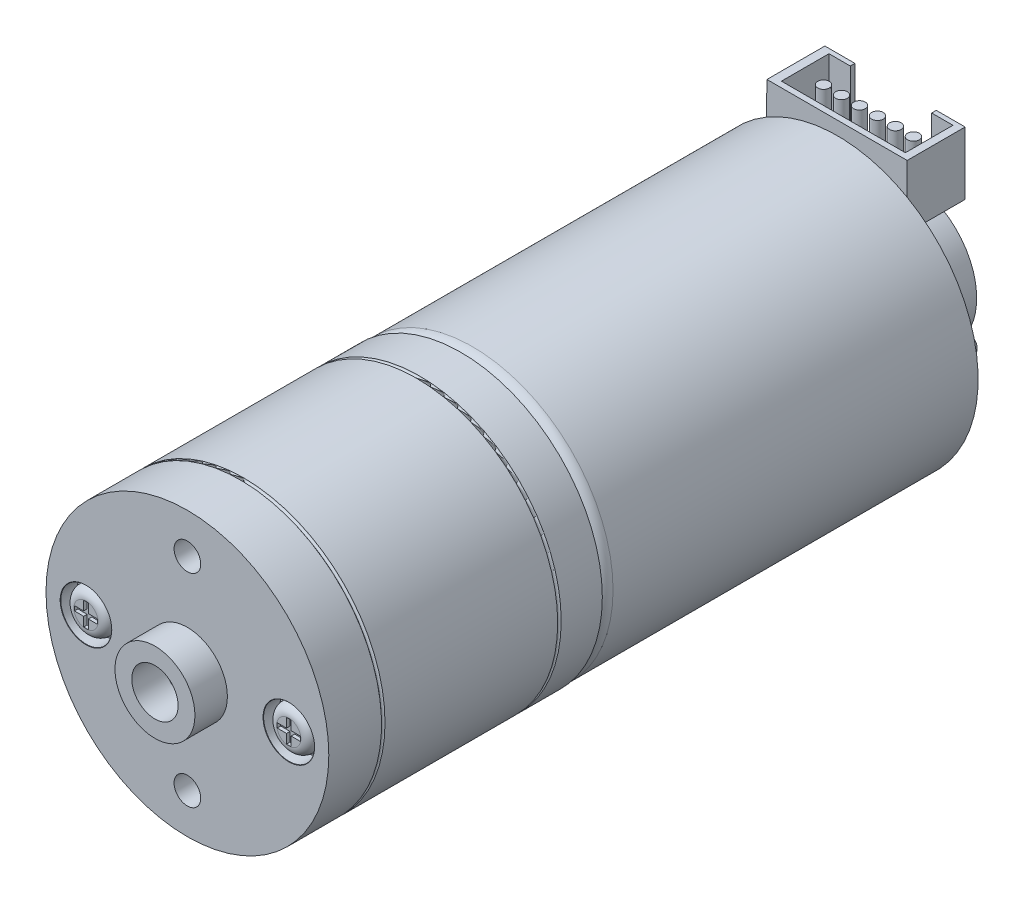
SolidWorks part; units mm, degrees
ref_plane "Front Plane" through (0, 0, 0) normal (0, 0, 1) x (1, 0, 0)
ref_plane "Top Plane" through (0, 0, 0) normal (0, 1, 0) x (1, 0, 0)
ref_plane "Right Plane" through (0, 0, 0) normal (1, 0, 0) x (0, 0, -1)
sketch "Sketch1" plane through (0, 0, 0) normal (0, 0, 1) x (1, 0, 0)
  circle A0 centre (0, 0) radius 12.125
  dimension "D1" = 24.25
extrude "Boss-Extrude1" add sketch "Sketch1" along normal blind 31
sketch "Sketch2" plane through (0, 0, 0) normal (0, 0, -1) x (-1, 0, 0)
  circle A1 centre (0, 0) radius 12.125
  circle A2 centre (0, 0) radius 12.125
  dimension "D1" = 0
fillet "Fillet2" radius 1 1 edges at (12.125, 0, 31)
shell "Shell1" thickness 1 removed face at (11.125, 0, 31)
ref_plane "Plane2" through (0, 0, 31) normal (0, 0, 1) x (1, 0, 0)
sketch "Sketch11" plane through (0, 0, 31) normal (0, 0, 1) x (1, 0, 0)
  circle A0 centre (0, 0) radius 12.2
  dimension "D1" = 24.4
extrude "Boss-Extrude4" add sketch "Sketch11" along normal blind 23.6 separate body
sketch "Sketch12" plane through (0, 0, 54.6) normal (0, 0, 1) x (1, 0, 0)
  circle A0 centre (0, 0) radius 3.45
  circle A1 centre (0, 0) radius 2
  dimension "D1" = 6.9
  dimension "D2" = 4
extrude "Boss-Extrude5" add sketch "Sketch12" along normal blind 2.8
sketch "Sketch14" plane through (0, 0, 54.6) normal (0, 0, 1) x (1, 0, 0)
  circle A0 centre (0, 0) radius 1.975
  dimension "D1" = 3.95
sketch "Sketch17" plane through (0, 0, 0) normal (0, 1, 0) x (1, 0, 0)
  line L0 (-12.2, -54.6) -> (-12.2, -49.9) construction
  line L1 (-12.2, -31) -> (-12.2, -54.6) construction
  line L2 (-12.2, -31) -> (-12.2, -34.7) construction
  circle A0 centre (-12.2, -49.9) radius 0.15
  circle A1 centre (-12.2, -34.7) radius 0.15
  dimension "D2" = 0.3
  dimension "D1" = 4.7
ref_axis "Axis1" through (0, 0, 54.6) along (0, 0, -1)
revolve "Cut-Revolve1" cut sketch "Sketch17" angle 360 about axis through (0, 0, 54.6) along (0, 0, -1)
sketch "Sketch18" plane through (0, 0, 54.6) normal (0, 0, 1) x (1, 0, 0)
  line L0 (0, 0) -> (8.75, 0) construction
  line L1 (0, 0) -> (0, 8.75) construction
  circle A1 centre (0, 8.75) radius 1.15
  circle A3 centre (0, -8.75) radius 1.15
  dimension "D3" = 2.3
extrude "Cut-Extrude7" cut sketch "Sketch18" against normal blind 10
sketch "Sketch19" plane through (0, 0, 0) normal (1, 0, 0) x (0, 0, -1)
  line L0 (-54.6, 9.9) -> (-53.4944, 10.0329)
  line L1 (-54.6, 9.9) -> (-54.6, 7.6) construction
  line L2 (-54.6, 12.2) -> (-54.6, -12.2) construction
  line L3 (-53.4944, 10.0329) -> (-53.399, 9.9)
  line L4 (-53.399, 9.9) -> (-54.6, 9.9)
sketch "Sketch20" plane through (0, 0, 54.6) normal (0, 0, 1) x (1, 0, 0)
  circle A0 centre (0, 8.75) radius 1.1448
curve "Helix/Spiral1" pitch 0.5 height 6 turns 12
sketch "Sketch21" plane through (0, 0, 54.6) normal (0, 0, 1) x (1, 0, 0)
  line L0 (0, 0) -> (0, -5.9622) construction
  circle A1 centre (8.75, 0) radius 2.25
  circle A2 centre (-8.75, 0) radius 2.25
  dimension "D1" = 4.5
hole_wizard "CBORE for M2 Cheese Head Screw1" positions "3DSketch1" profile "Sketch23" counterbore size "M2" standard "DIN"
sketch3d "3DSketch1"
  point P0 (-8.75, 0, 54.6)
  point P3 (8.75, 0, 54.6)
sketch "Sketch23" plane through (-8.75, 0, 54.6) normal (1, 0, 0) x (0, -1, 0)
  line L0 (0, 0) -> (0, 5.7811)
  line L1 (0, 5.7811) -> (1.3, 5)
  line L2 (1.3, 5) -> (1.3, 1.4)
  line L3 (1.3, 1.4) -> (2.2, 1.4)
  line L5 (2.2, 1.4) -> (2.2, 0.025)
  line L6 (2.2, 0.025) -> (2.225, 0)
  line L7 (2.225, 0) -> (0, 0)
  line L8 (-2.2, 0.025) -> (-2.225, 0) construction
  line L10 (0, 5.7811) -> (-1.3, 5) construction
  line L11 (0, -6.35) -> (0, 107.95) construction
  dimension "Hole Dia." = 2.6
  dimension "Hole Depth" = 5
  dimension "C'Bore Dia." = 4.4
  dimension "C'Bore Depth" = 1.4
  dimension "Near C'Sink Dia." = 4.45
  dimension "Near C'Sink Angle" = 90
  dimension "Drill Angle" = 118
sketch "Sketch24" plane through (0, 0, 53.2) normal (0, 0, 1) x (1, 0, 0)
  circle A0 centre (-8.75, 0) radius 1.8422
extrude "Boss-Extrude7" add sketch "Sketch24" along normal blind 1.4
sketch "Sketch25" plane through (0, 0, 54.6) normal (0, 0, 1) x (1, 0, 0)
  line L0 (-8.55, 0.2) -> (-7.75, 0.2)
  line L1 (-9.75, 0.2) -> (-8.95, 0.2)
  line L2 (-9.75, 0.2) -> (-9.75, -0.2)
  line L3 (-9.75, -0.2) -> (-8.95, -0.2)
  line L4 (-7.75, 0.2) -> (-7.75, -0.2)
  line L7 (-8.95, 1) -> (-8.55, 1)
  line L8 (-8.95, 1) -> (-8.95, 0.2)
  line L9 (-8.95, -1) -> (-8.55, -1)
  line L10 (-8.55, 1) -> (-8.55, 0.2)
  line L12 (-8.55, -0.2) -> (-7.75, -0.2)
  line L13 (-8.95, -0.2) -> (-8.95, -1)
  line L16 (-8.55, -0.2) -> (-8.55, -1)
  point P0 (-8.75, 0)
  point P5 (-8.75, 0)
extrude "Cut-Extrude9" cut sketch "Sketch25" against normal blind 0.3
fillet "Fillet3" radius 0.8 1 edges at (-6.9078, 0, 54.6)
mirror "Mirror2" about plane through (0, 0, 0) normal (1, 0, 0) of "Fillet3", "Cut-Extrude9", "Boss-Extrude7"
ref_plane "Plane3" through (0, 0, 0) normal (0, 0, -1) x (-1, 0, 0)
sketch "Sketch26" plane through (0, 0, 0) normal (0, 0, -1) x (-1, 0, 0)
  circle A0 centre (0, 0) radius 12.125
extrude "Boss-Extrude8" add sketch "Sketch26" along normal blind 1.5
ref_plane "Plane4" through (0, 0, -1.5) normal (0, 0, -1) x (-1, 0, 0)
sketch "Sketch27" plane through (0, 0, -1.5) normal (0, 0, -1) x (-1, 0, 0)
  circle A0 centre (0, 0) radius 6
  dimension "D1" = 12
extrude "Boss-Extrude9" add sketch "Sketch27" along normal blind 5 from offset 1 separate body contours A0
sketch "Sketch28" plane through (0, 0, -1.5) normal (0, 0, -1) x (-1, 0, 0)
  circle A0 centre (0, 0) radius 0.75
extrude "Boss-Extrude10" add sketch "Sketch28" along normal blind 8 contours A0
sketch "Sketch29" plane through (0, 0, -1.5) normal (0, 0, -1) x (-1, 0, 0)
  line L1 (6.0994, 13.2874) -> (-6, 13.2874)
  line L2 (6.0994, 13.2874) -> (6.1786, 7.872)
  line L3 (6.1786, 7.872) -> (-6, 7.872)
  line L4 (-6, 13.2874) -> (-6, 7.872)
  line L5 (6.0994, 13.2874) -> (-6, 7.872) construction
  line L6 (6.1786, 7.872) -> (-6, 13.2874) construction
  point P0 (0, 10.0459)
extrude "Boss-Extrude11" add sketch "Sketch29" along normal blind 5
ref_plane "Plane5" through (0, 13.2874, 0) normal (0, 1, 0) x (1, 0, 0)
sketch "Sketch31" plane through (0, 13.2874, 0) normal (0, 1, 0) x (1, 0, 0)
  line L1 (5.3489, 6.1016) -> (-5.3489, 6.1016)
  line L2 (5.3489, 6.1016) -> (5.3489, 1.9988)
  line L3 (5.3489, 1.9988) -> (-5.3489, 1.9988)
  line L4 (-5.3489, 6.1016) -> (-5.3489, 1.9988)
  line L5 (5.3489, 6.1016) -> (-5.3489, 1.9988) construction
  line L6 (5.3489, 1.9988) -> (-5.3489, 6.1016) construction
  line L7 (3.5118, 10.53) -> (-3.5118, 10.53)
  line L8 (3.5118, 10.53) -> (3.5118, 3.7483)
  line L9 (3.5118, 3.7483) -> (-3.5118, 3.7483)
  line L10 (-3.5118, 10.53) -> (-3.5118, 3.7483)
  line L11 (3.5118, 10.53) -> (-3.5118, 3.7483) construction
  line L12 (3.5118, 3.7483) -> (-3.5118, 10.53) construction
  point P0 (0, 4.0502)
  point P5 (0, 7.1391)
  line M3 (6, 6.5) -> (-6.0994, 6.5)
extrude "Cut-Extrude10" cut sketch "Sketch31" against normal blind 4.5 contours L10 L1 L4 L3 L2 L8 L9 | L1 L10 L9 L8 | L10 L1 L8 M3 region at (0, 13.2874, -3.5218) region at (0, 13.2874, -4.9249) region at (0, 13.2874, -6.3008)
sketch "Sketch32" plane through (0, 8.7874, 0) normal (0, 1, 0) x (1, 0, 0)
  circle A0 centre (3.9803, 4.0556) radius 0.5
  circle A1 centre (2.4303, 4.0556) radius 0.5
  circle A2 centre (0.8803, 4.0556) radius 0.5
  circle A3 centre (-0.6697, 4.0556) radius 0.5
  circle A4 centre (-2.2197, 4.0556) radius 0.5
  circle A5 centre (-3.7697, 4.0556) radius 0.5
  dimension "D1" = 6
extrude "Boss-Extrude12" add sketch "Sketch32" along normal blind 4 contours A0 | A1 | A2 | A3 | A4 | A5
sketch "Sketch33" plane through (0, 0, -1.5) normal (0, 0, -1) x (-1, 0, 0)
  line L0 (5.822, -4.3383) -> (7.2246, -1.6864) construction
  line L1 (5.159, -3.9877) -> (6.5616, -1.3357)
  line L2 (6.485, -4.6889) -> (7.8876, -2.037)
  line L3 (-5.736, -4.291) -> (-7.2951, -1.7279) construction
  line L4 (-6.3768, -4.6808) -> (-7.9358, -2.1177)
  line L5 (-5.0952, -3.9012) -> (-6.6543, -1.3382)
  line L6 (0, 0) -> (0, -6.9518) construction
  line L7 (-8.5109, 0.5462) -> (-10.6566, 0.5462)
  line L8 (-8.5109, 0.5462) -> (-8.5109, -0.5462)
  line L9 (-8.5109, -0.5462) -> (-10.6566, -0.5462)
  line L10 (-10.6566, 0.5462) -> (-10.6566, -0.5462)
  line L11 (-8.5109, 0.5462) -> (-10.6566, -0.5462) construction
  line L12 (-8.5109, -0.5462) -> (-10.6566, 0.5462) construction
  line L13 (10.6566, 0.5462) -> (10.6566, -0.5462)
  line L14 (8.5109, -0.5462) -> (10.6566, -0.5462)
  line L15 (8.5109, 0.5462) -> (8.5109, -0.5462)
  line L16 (8.5109, 0.5462) -> (10.6566, 0.5462)
  line L17 (2.5787, -9.2868) -> (1.7583, -9.2868)
  line L18 (-2.5787, -7.2673) -> (-1.7583, -7.2673)
  line L19 (-2.5787, -7.2673) -> (-2.5787, -9.2868)
  line L20 (-2.5787, -9.2868) -> (-1.7583, -9.2868)
  line L21 (-1.7583, -7.2673) -> (-1.7583, -9.2868)
  line L22 (-2.5787, -7.2673) -> (-1.7583, -9.2868) construction
  line L23 (-2.5787, -9.2868) -> (-1.7583, -7.2673) construction
  line L24 (2.5787, -7.2673) -> (2.5787, -9.2868)
  line L25 (1.7583, -7.2673) -> (1.7583, -9.2868)
  line L26 (2.5787, -7.2673) -> (1.7583, -7.2673)
  arc A0 (5.159, -3.9877) -> (6.485, -4.6889) centre (5.822, -4.3383) ccw
  arc A1 (7.8876, -2.037) -> (6.5616, -1.3357) centre (7.2246, -1.6864) ccw
  arc A2 (-6.3768, -4.6808) -> (-5.0952, -3.9012) centre (-5.736, -4.291) ccw
  arc A3 (-6.6543, -1.3382) -> (-7.9358, -2.1177) centre (-7.2951, -1.7279) ccw
  point P2 (6.5233, -3.0123)
  point P7 (-6.5155, -3.0095)
  point P19 (-9.5838, 0)
  point P26 (-2.1685, -8.2771)
extrude "Boss-Extrude13" add sketch "Sketch33" along normal blind 4 contours L2 A1 L1 A0 | A3 L4 A2 L5 region at (-6.5233, -3.0123, -1.5)
extrude "Boss-Extrude14" add sketch "Sketch33<4>" along normal blind 1
sketch "Sketch33<4>" plane through (0, 0, -1.5) normal (0, 0, -1) x (-1, 0, 0) same geometry as "Sketch33"
